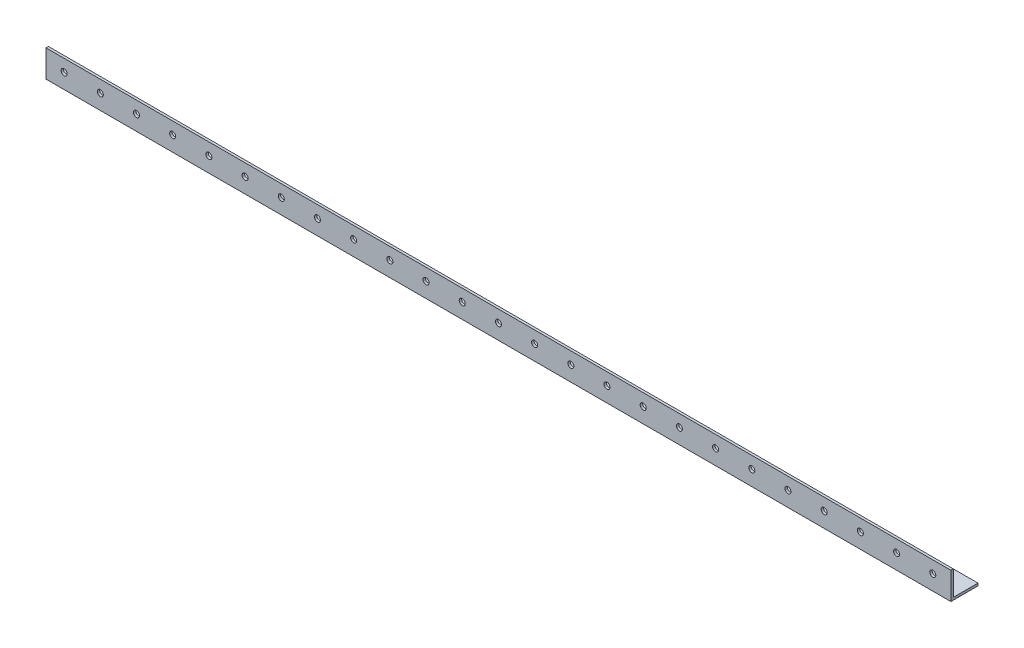
SolidWorks part; units mm, degrees
ref_plane "Спереди" through (0, 0, 0) normal (0, 0, 1) x (1, 0, 0)
ref_plane "Сверху" through (0, 0, 0) normal (0, 1, 0) x (1, 0, 0)
ref_plane "Справа" through (0, 0, 0) normal (1, 0, 0) x (0, 0, -1)
sketch "Эскиз1" plane through (0, 0, 0) normal (1, 0, 0) x (0, 0, -1)
  line L0 (0, 0) -> (0, 45)
  line L1 (0, 0) -> (45, 0)
  dimension "D1" = 45
  dimension "D2" = 45
extrude "Вытянуть-Тонкостенный1" add sketch "Эскиз1" along normal blind 1500 thin thin type one direction reverse wall 4
sketch "Эскиз2" plane through (0, 0, 0) normal (0, 0, 1) x (1, 0, 0)
  circle A0 centre (30, 25) radius 5
  circle A1 centre (90, 25) radius 5
  circle A2 centre (150, 25) radius 5
  circle A3 centre (210, 25) radius 5
  circle A8 centre (270, 25) radius 5
  circle A9 centre (330, 25) radius 5
  circle A10 centre (390, 25) radius 5
  circle A11 centre (450, 25) radius 5
  circle A12 centre (510, 25) radius 5
  circle A13 centre (570, 25) radius 5
  circle A14 centre (630, 25) radius 5
  circle A15 centre (690, 25) radius 5
  circle A16 centre (750, 25) radius 5
  circle A17 centre (810, 25) radius 5
  circle A18 centre (870, 25) radius 5
  circle A19 centre (930, 25) radius 5
  circle A20 centre (990, 25) radius 5
  circle A21 centre (1050, 25) radius 5
  circle A22 centre (1110, 25) radius 5
  circle A23 centre (1170, 25) radius 5
  circle A24 centre (1230, 25) radius 5
  circle A25 centre (1290, 25) radius 5
  circle A26 centre (1350, 25) radius 5
  circle A27 centre (1410, 25) radius 5
  circle A28 centre (1470, 25) radius 5
  dimension "D1" = 25
extrude "Вырез-Вытянуть1" cut sketch "Эскиз2" against normal through all
